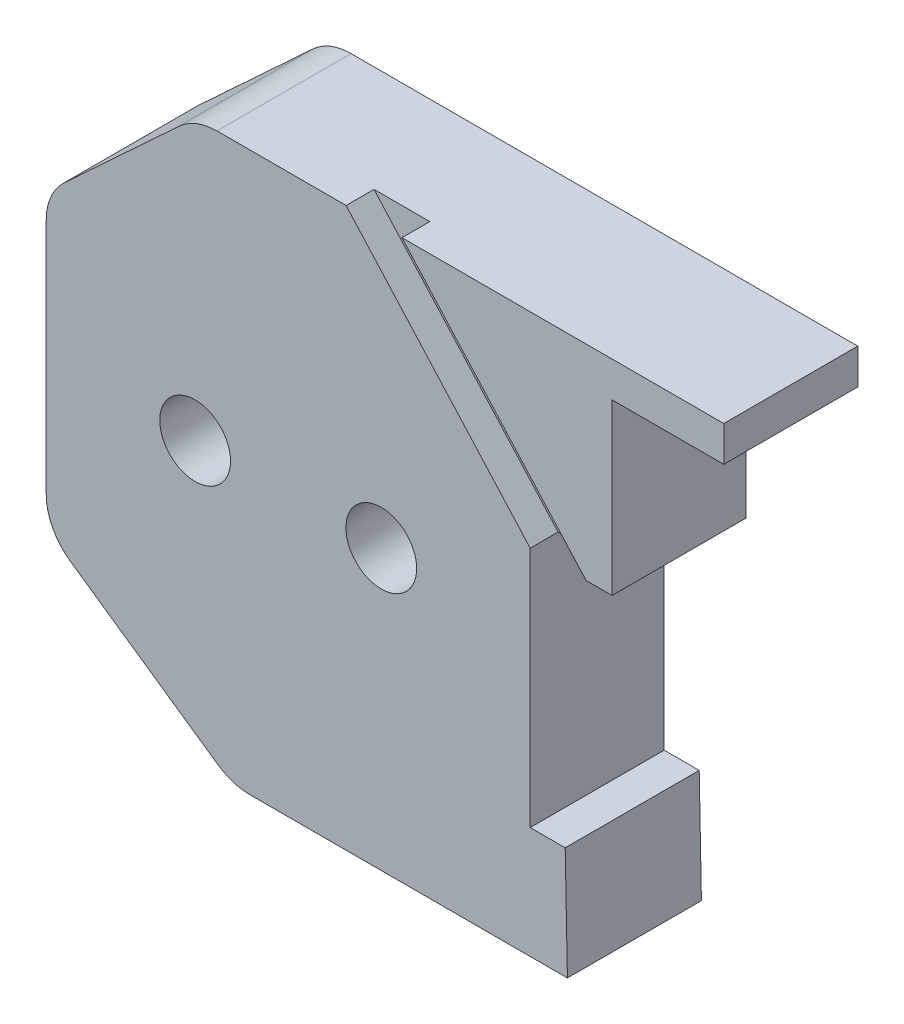
SolidWorks part; units mm, degrees
ref_plane "Front Plane" through (0, 0, 0) normal (0, 0, 1) x (1, 0, 0)
ref_plane "Top Plane" through (0, 0, 0) normal (0, 1, 0) x (1, 0, 0)
ref_plane "Right Plane" through (0, 0, 0) normal (1, 0, 0) x (0, 0, -1)
sketch "Sketch2" plane through (0, 0, 0) normal (0, 0, 1) x (1, 0, 0)
  line L1 (-2.5, 7.5) -> (-16.7, 7.5)
  line L2 (-20.7, 3.7934) -> (-20.7, -4.0316)
  line L3 (-15.7, -7.5) -> (-6.7, -7.5)
  line L4 (-6.7, -7.5) -> (-4.2, -5.6)
  line L5 (-2.5, 7.5) -> (0, 7.5)
  line L7 (0, 7) -> (0, 7.5)
  line L8 (-20.7, 3.7934) -> (-16.7, 7.5)
  line L9 (-20.7, -4.0316) -> (-15.7, -7.5)
  arc A1 (-4.2, -5.6) -> (7, 0) centre (0, 0) ccw
  arc A2 (7, 0) -> (0, 7) centre (0, 0) ccw
  dimension "D1" = 7
  dimension "D2" = 4
  dimension "D3" = 5
  dimension "D4" = 7.5
  dimension "D5" = 15
  dimension "D7" = 2.5
  dimension "D8" = 14
extrude "Boss-Extrude1" add sketch "Sketch2" along normal blind 2 contours A1 A2 L7 L5 L1 L8 L2 L9 L3 L4
sketch "Sketch4" plane through (0, 0, 2) normal (0, 0, 1) x (1, 0, 0)
  line L7 (-15.7, -7.5) -> (-6.7, -7.5)
  line L8 (-6.7, -7.5) -> (-6.7591, -4.5)
  line L9 (-6.7591, -4.5) -> (-7.7, -4.5)
  line L10 (-16.7, 7.5) -> (-2.5, 7.5)
  line L13 (-5.5, 2) -> (-5.5, 5.3)
  line L14 (-5.5, 5.3) -> (-2.5, 5.3)
  line L21 (-20.7, -4.0316) -> (-15.7, -7.5)
  line L24 (-16.7, 7.5) -> (-20.7, 3.7934)
  line L25 (-20.7, -4.0316) -> (-20.7, 3.7934)
  line L26 (-7.7, 2) -> (-5.5, 2)
  line L29 (-7.7, 2) -> (-7.7, -4.5)
  line L30 (-2.5, 7.5) -> (-2.5, 5.3)
  point P2 (-5.5, 3.65)
  dimension "D1" = 13
  dimension "D2" = 2.5
  dimension "D3" = 3
  dimension "D4" = 3
  dimension "D5" = 3.3
  dimension "D6" = 2.2
extrude "Boss-Extrude2" add sketch "Sketch4" along normal blind 8
ref_point "Point1"
sketch "Sketch22" plane through (0, 0, 2) normal (0, 0, 1) x (1, 0, 0)
  line L0 (0, 5.3) -> (-14, 5.3) construction
  line L1 (0, 4) -> (-14, 4) construction
  line L2 (-14, 4) -> (-14, 5.3) construction
  circle A0 centre (0, 0) radius 5.3 construction
  circle A1 centre (0, 0) radius 4 construction
  dimension "D1" = 14
  dimension "D2" = 10.6
  dimension "D3" = 8
sketch "Sketch24" plane through (0, 0, 2) normal (0, 0, 1) x (1, 0, 0)
  circle A0 centre (0, 0) radius 3.9
  dimension "D1" = 7.8
extrude "Boss-Extrude5" add sketch "Sketch24" along normal blind 4.4
sketch "Sketch29" plane through (-5.5, 0, 0) normal (1, 0, 0) x (0, 0, -1)
  line L0 (-1.9279, 3.9758) -> (-10, 3.9758) construction
  line L1 (-10, 2) -> (-10, 5.3) construction
sketch "Sketch30" plane through (-5.5, 0, 0) normal (1, 0, 0) x (0, 0, -1)
  line L0 (-6.4086, 3.9758) -> (-6.4086, 5.3)
  line L1 (-6.4086, 3.9758) -> (-2, 3.9758)
  line L2 (-6.4086, 5.3) -> (-2, 5.3)
  line L3 (-2, 3.9758) -> (-2, 5.3)
  line L6 (-2, 2) -> (-2, 5.3) construction
  line L7 (-10, 5.3) -> (-2, 5.3) construction
  dimension "D1" = 4.4086
extrude "Cut-Extrude12" cut sketch "Sketch30" against normal blind 16
ref_plane "Plane1" through (0, 0, 10) normal (0, 0, 1) x (1, 0, 0)
sketch "Sketch8" plane through (0, 0, 2) normal (0, 0, 1) x (1, 0, 0)
  circle A1 centre (0, 0) radius 3.8
  circle A2 centre (0, 0) radius 2.5
sketch "Sketch28" plane through (0, 0, 6.4) normal (0, 0, 1) x (1, 0, 0)
  line L0 (-1, 0.9798) -> (-1, -0.9798)
  arc A0 (-1, -0.9798) -> (-1, 0.9798) centre (0, 0) ccw
  dimension "D1" = 1
  dimension "D2" = 1.4
extrude "Cut-Extrude11" cut sketch "Sketch28" against normal through all
sketch "Sketch33" plane through (0, 0, 10) normal (0, 0, 1) x (1, 0, 0)
  line L0 (-7, 2) -> (-0.5657, -5.1566) construction
  line L2 (-8.2591, -4.5) -> (-2.6001, 3.0469) construction
  dimension "D1" = 1.5
  dimension "D2" = 1.5
fillet "Fillet1" radius 1.5 9 edges at (-11.2, -7.5, 0) (-8.35, 7.5, 0) (-18.7, 5.6467, 0) (-18.2, -5.7658, 0) (-20.7, -0.1191, 0) (-15.7, -7.5, 5) (-20.7, -4.0316, 5) (-20.7, 3.7934, 5) (-16.7, 7.5, 5)
sketch "Sketch34" plane through (0, 2, 0) normal (0, -1, 0) x (1, 0, 0)
  line L4 (-7.7, 10) -> (-5.5, 10) construction
  line L5 (-6.2, 10.75) -> (-7.7, 10.75)
  line L6 (-6.2, 10.75) -> (-6.2, 9.25)
  line L7 (-6.2, 9.25) -> (-7.7, 9.25)
  line L8 (-7.7, 10.75) -> (-7.7, 9.25)
  line L9 (-6.2, 10.75) -> (-7.7, 9.25) construction
  line L10 (-6.2, 9.25) -> (-7.7, 10.75) construction
  line L12 (-7.7, 10) -> (-7.7, 2) construction
  point P0 (-6.95, 10)
  dimension "D1" = 1.5
  dimension "D2" = 1.5
extrude "Cut-Extrude13" cut sketch "Sketch34" along direction (0.6686, -0.7436, 0) on the side against the normal blind 8
sketch "Sketch35" plane through (0, -4.5, 0) normal (0, 1, 0) x (1, 0, 0)
  circle A0 centre (-8.2591, -10) radius 0.75
sketch "Sketch36" plane through (0, 0, 10) normal (0, 0, 1) x (1, 0, 0)
  line L0 (-20.7, 3.1384) -> (-20.7, -3.2466) construction
  line L1 (-12.6449, 7.5) -> (-16.1119, 7.5) construction
  line L2 (-7.7, -4.5) -> (-7.7, 2) construction
  circle A0 centre (-11.7, 0) radius 0.95
  circle A1 centre (-16.7, 0) radius 0.95
  dimension "D1" = 4
  dimension "D2" = 5
  dimension "D5" = 1.9
  dimension "D3" = 4
  dimension "D4" = 7.5
extrude "Cut-Extrude15" cut sketch "Sketch36" against normal blind 8
sketch "Sketch37" plane through (0, 0, 0) normal (0, 0, -1) x (-1, 0, 0)
  circle A0 centre (11.7, 0) radius 2
  circle A1 centre (16.7, 0) radius 2
  dimension "D1" = 4
extrude "Cut-Extrude16" cut sketch "Sketch37" against normal blind 4.5
sketch "Sketch38" plane through (0, 0, 10) normal (0, 0, 1) x (1, 0, 0)
  line L0 (-5.5, 5.3) -> (-2.5, 5.3)
  line L1 (-5.5, 5.3) -> (-5.5, 6.55)
  line L2 (-2.5, 5.3) -> (-2.5, 6.55)
  line L3 (-5.5, 6.55) -> (-2.5, 6.55)
  dimension "D1" = 1.25
extrude "Cut-Extrude17" cut sketch "Sketch38" against normal blind 3.6
ref_plane "Plane2" through (0, 0, 6.4) normal (0, 0, 1) x (1, 0, 0)
split "Split1" trim tools "Plane2" bodies to split 129 resulting bodies 130 131
delete or keep bodies "Body-Delete/Keep 1" type delete bodies bodies 131
